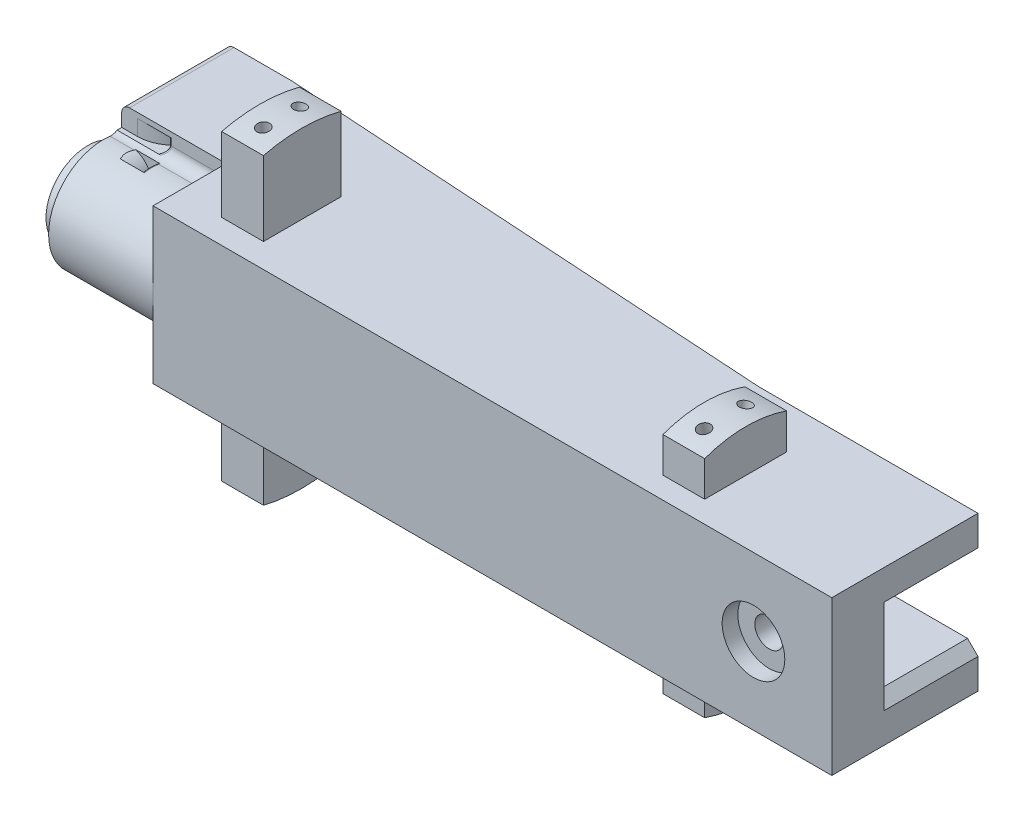
SolidWorks part; units mm, degrees
material "ABS"
ref_plane "Plan de face" through (0, 0, 0) normal (0, 0, 1) x (1, 0, 0)
ref_plane "Plan de dessus" through (0, 0, 0) normal (0, 1, 0) x (1, 0, 0)
ref_plane "Plan de droite" through (0, 0, 0) normal (1, 0, 0) x (0, 0, -1)
sketch "Esquisse1" plane through (0, 0, 0) normal (0, 0, 1) x (1, 0, 0)
  line L0 (-150, -14.75) -> (-150, 14.75)
  line L1 (-150, 14.75) -> (0, 14.75)
  line L2 (0, 14.75) -> (0, -14.75)
  line L3 (-150, 0) -> (0, 0) construction
  line L4 (-150, -14.75) -> (0, -14.75)
  dimension "D1" = 29.5
  dimension "D2" = 150
extrude "ForearmMain" add sketch "Esquisse1" along normal blind 34
ref_plane "Plan1" through (0, 0, 0) normal (0, -1, 0) x (-1, 0, 0)
ref_plane "Plan2" through (0, 0, 23.5) normal (0, 0, -1) x (-1, 0, 0)
sketch "Esquisse2" plane through (-150, 0, 0) normal (-1, 0, 0) x (0, 0, 1)
  line L0 (0, 14.75) -> (0, -14.75) construction
  line L1 (20, 9.8995) -> (20, 14.75)
  line L2 (0, 0) -> (49.5, 0) construction
  line L3 (20, 14.75) -> (49.5, 14.75)
  line L4 (49.5, 14.75) -> (49.5, -14.75)
  line L5 (49.5, -14.75) -> (20, -14.75)
  line L6 (20, -14.75) -> (20, -9.8995)
  line L7 (34, 14.75) -> (0, 14.75) construction
  line L8 (34, -14.75) -> (0, -14.75) construction
  arc A0 (20, -9.8995) -> (20, 9.8995) centre (23.5, 0) ccw
  point P8 (20, 12.3247)
  point P13 (20, -12.3247)
  dimension "D1" = 10.5
  dimension "D2" = 23.5
  dimension "D3" = 3.5
extrude "Enlèv. mat.-Extru.1" cut sketch "Esquisse2" against normal blind 20
sketch "Esquisse3" plane through (-150, 0, 0) normal (-1, 0, 0) x (0, 0, 1)
  circle A0 centre (23.5, 0) radius 8
  dimension "D1" = 16
extrude "Boss.-Extru.2" add sketch "Esquisse3" along normal blind 3
sketch "Esquisse4" plane through (-153, 0, 0) normal (-1, 0, 0) x (0, 0, 1)
  line L1 (0, 0) -> (45.6879, 0) construction
  circle A0 centre (29, 0) radius 1.025
  circle A1 centre (23.5, 0) radius 8 construction
  dimension "D1" = 2.05
  dimension "D2" = 5.5
extrude "Enlèv. mat.-Extru.2" cut sketch "Esquisse4" against normal blind 10
chamfer "Chanfrein1" distance 0.3 angle 45 1 edges at (-153, 0, 30.025)
pattern_circular "Répétition circulaire1" count 3 over 360 about axis through (-153, 0, 23.5) along (-1, 0, 0) of "Chanfrein1", "Enlèv. mat.-Extru.2"
fillet "Congé1" radius 2 2 edges at (-140, 9.8995, 20) (-140, -9.8995, 20)
sketch "Esquisse5" plane through (0, -14.75, 0) normal (0, -1, 0) x (-1, 0, 0)
  line L0 (147, 0) -> (150, 0)
  line L1 (150, -20) -> (147, -20)
  line L2 (150, -31.5) -> (150, -15.5) construction
  line L3 (140, -13) -> (140, -7)
  line L4 (150, -20) -> (150, -22.5)
  line L5 (150, -22.5) -> (148.5, -22.5)
  line L6 (137.5, -11.5) -> (137.5, -8.5)
  line L7 (130, -20) -> (150, -20) construction
  line L8 (150, -20) -> (150, 0) construction
  line L9 (150, 0) -> (150, 2.5)
  line L10 (150, 2.5) -> (148.5, 2.5)
  line L11 (150, 0) -> (0, 0) construction
  arc A0 (140, -13) -> (147, -20) centre (147, -13) ccw
  arc A1 (137.5, -11.5) -> (148.5, -22.5) centre (148.5, -11.5) ccw
  arc A2 (140, -7) -> (147, 0) centre (147, -7) cw
  arc A3 (137.5, -8.5) -> (148.5, 2.5) centre (148.5, -8.5) cw
  dimension "D4" = 7
  dimension "D5" = 11
  dimension "D6" = 7
  dimension "D7" = 11
  dimension "D1" = 2.5
  dimension "D2" = 2.5
  dimension "D3" = 10
  dimension "D8" = 2.5
extrude "ZiptieHole1" cut sketch "Esquisse5" against normal blind 3 from offset 1 offset against normal yes
mirror "ZiptieSymmetry" about plane through (0, 0, 0) normal (0, -1, 0) of "ZiptieHole1"
sketch "Esquisse6" plane through (0, 0, 34) normal (0, 0, 1) x (1, 0, 0)
  line L0 (-57.8936, 10.7) -> (-119.0286, 10.7) construction
  line L1 (-57.0745, 0) -> (-113.5036, 0) construction
  line L2 (-139.5, -5.2) -> (-139.5, 5.2)
  line L3 (-147.5, 13.2) -> (-162, 13.2)
  line L4 (-162, 13.2) -> (-162, 10.7)
  line L5 (-13.475, 0) -> (13.475, 0) construction
  line L6 (-162, -10.7) -> (-147, -10.7)
  line L7 (-162, 10.7) -> (-147, 10.7)
  line L8 (-142, 5.7) -> (-142, -5.7)
  line L9 (-162, -13.2) -> (-162, -10.7)
  line L10 (-147.5, -13.2) -> (-162, -13.2)
  line L11 (-150, 10.5) -> (-150, -10.5) construction
  arc A0 (-147, 10.7) -> (-142, 5.7) centre (-147, 5.7) cw
  arc A1 (-139.5, 5.2) -> (-147.5, 13.2) centre (-147.5, 5.2) ccw
  arc A2 (-139.5, -5.2) -> (-147.5, -13.2) centre (-147.5, -5.2) cw
  arc A3 (-147, -10.7) -> (-142, -5.7) centre (-147, -5.7) ccw
  point P23 (-142, 0)
  point P25 (-139.5, 0)
  dimension "D1" = 5
  dimension "D4" = 8
  dimension "D2" = 10.7
  dimension "D3" = 2.5
  dimension "D5" = 2.5
  dimension "D6" = 8
  dimension "D7" = 20
extrude "ZiptieHole2" cut sketch "Esquisse6" against normal blind 3 from offset 9 offset against normal yes
fillet "Congé3" radius 1.5 2 edges at (-150, 14.75, 10) (-150, -14.75, 10)
fillet "Congé13" radius 0.4 9 edges at (-141.5179, -13.0798, 20) (-141.7114, -11.6368, 20.1554) (-141.5179, -12.25, 0) (-141.5179, 12.25, 0) (-141.7114, 11.6368, 20.1554)
ref_plane "BackScrewsPlane" through (-117.5, 0, 0) normal (-1, 0, 0) x (0, 0, 1)
ref_plane "FrontScrewsPlane" through (-32.5, 0, 0) normal (-1, 0, 0) x (0, 0, 1)
sketch "Esquisse7" plane through (-32.5, 0, 0) normal (-1, 0, 0) x (0, 0, 1)
  line L0 (16.9395, 22.3646) -> (21.9137, 23.2417) construction
  line L1 (21.9137, 23.2417) -> (27.0552, 22.3351) construction
  line L2 (25.972, 22.5261) -> (25.972, -22.5261) construction
  line L3 (27.0552, -22.335) -> (21.9136, -23.2417) construction
  line L4 (21.9136, -23.2417) -> (16.9395, -22.3646) construction
  line L5 (18.0228, -22.5556) -> (18.0228, 22.5556) construction
  line L6 (16.9395, 22.3646) -> (21.9137, 23.2417) construction
  line L7 (21.9137, 23.2417) -> (27.0552, 22.3351) construction
  line L8 (25.972, 22.5261) -> (25.972, -22.5261) construction
  line L9 (27.0552, -22.335) -> (21.9136, -23.2417) construction
  line L10 (21.9136, -23.2417) -> (16.9395, -22.3646) construction
  line L11 (18.0228, -22.5556) -> (18.0228, 22.5556) construction
  line L12 (18.0228, -22.5556) -> (19.2697, -15.4845) construction
  line L13 (25.972, -22.5261) -> (24.7953, -15.8529) construction
  line L14 (14.1382, -21.5513) -> (14.1382, -14.75)
  line L15 (14.1382, -14.75) -> (29.8513, -14.75)
  line L16 (29.8513, -14.75) -> (29.8513, -21.492)
  line L17 (14.1382, -14.75) -> (0, -14.75) construction
  arc A0 (14.1382, -21.5513) -> (29.8513, -21.492) centre (21.9117, 0.5007) ccw
  dimension "D1" = 4
  dimension "D2" = 4
extrude "Boss.-Extru.3" add sketch "Esquisse7" against normal mid plane 8 contours L14 A0 L16 L15
ref_plane "Plan7" through (-32.5, -22.5556, 18.0228) normal (0, 0.9848, 0.1736) x (1, 0, 0)
ref_plane "Plan8" through (-32.5, -22.5261, 25.972) normal (0, 0.9848, -0.1736) x (1, 0, 0)
hole_wizard "Dégagement M23" positions "Esquisse30" profile "Esquisse31" hole size "M2" standard "Ansi Metric"
sketch "Esquisse30" plane through (-32.5, -22.5556, 18.0228) normal (0, 0.9848, 0.1736) x (1, 0, 0)
  point P0 (0, 0)
sketch "Esquisse31" plane through (-32.5, -22.5556, 18.0228) normal (1, 0, 0) x (0, 0.1736, -0.9848)
  line L0 (0, 0) -> (0, 12)
  line L1 (0, 12) -> (1.2, 12)
  line L2 (1.2, 12) -> (1.2, 0)
  line L4 (1.2, 0) -> (0, 0) construction
  line L5 (1.2, 0) -> (0, 0) construction
  line L6 (1.2, 0) -> (1.2, -1.2)
  line L7 (1.2, -1.2) -> (0, -1.2)
  line L8 (0, 0) -> (0, -1.2)
  line L10 (0, 12) -> (-1.2, 12) construction
  line L11 (0, -6.35) -> (0, 107.95) construction
  dimension "Diamètre du perçage" = 2.4
  dimension "Profondeur du perçage" = 12
  dimension "Angle de pointe" = 180
hole_wizard "Dégagement M24" positions "Esquisse32" profile "Esquisse33" hole size "M2" standard "Ansi Metric"
sketch "Esquisse32" plane through (-32.5, -22.5261, 25.972) normal (0, 0.9848, -0.1736) x (1, 0, 0)
  point P0 (0, 0)
sketch "Esquisse33" plane through (-32.5, -22.5261, 25.972) normal (1, 0, 0) x (0, -0.1736, -0.9848)
  line L0 (0, 0) -> (0, 12)
  line L1 (0, 12) -> (1.2, 12)
  line L2 (1.2, 12) -> (1.2, 0)
  line L5 (1.2, 0) -> (0, 0)
  line L10 (0, 12) -> (-1.2, 12) construction
  line L11 (0, -6.35) -> (0, 107.95) construction
  dimension "Diamètre du perçage" = 2.4
  dimension "Profondeur du perçage" = 12
  dimension "Angle de pointe" = 180
sketch "Esquisse34" plane through (-32.5, -22.5556, 18.0228) normal (0, 0.9848, 0.1736) x (1, 0, 0)
  line L0 (-1.1836, 2.05) -> (-4, 2.05)
  line L1 (-1.1836, 2.05) -> (-2.3671, 0) construction
  line L2 (-2.3671, 0) -> (-1.1836, -2.05) construction
  line L3 (-1.1836, -2.05) -> (1.1836, -2.05)
  line L4 (1.1836, -2.05) -> (2.3671, 0)
  line L5 (2.3671, 0) -> (1.1836, 2.05)
  line L6 (1.1836, 2.05) -> (-1.1836, 2.05)
  line L7 (-4, 2.05) -> (-4, -2.05)
  line L8 (-4, -2.05) -> (-1.1836, -2.05)
  line L9 (-4, 5.181) -> (-4, -10.2934) construction
  circle A0 centre (0, 0) radius 2.05 construction
  dimension "D1" = 4.1
extrude "Enlèv. mat.-Extru.9" cut sketch "Esquisse34" along normal blind 1.7 from offset 3
sketch "Esquisse35" plane through (-32.5, -22.5261, 25.972) normal (0, 0.9848, -0.1736) x (1, 0, 0)
  line L0 (-1.1836, 2.05) -> (-4, 2.05)
  line L1 (-1.1836, 2.05) -> (-2.3671, 0) construction
  line L2 (-2.3671, 0) -> (-1.1836, -2.05) construction
  line L3 (-1.1836, -2.05) -> (1.1836, -2.05)
  line L4 (1.1836, -2.05) -> (2.3671, 0)
  line L5 (2.3671, 0) -> (1.1836, 2.05)
  line L6 (1.1836, 2.05) -> (-1.1836, 2.05)
  line L7 (-4, 2.05) -> (-4, -2.05)
  line L8 (-4, -2.05) -> (-1.1836, -2.05)
  line L9 (-4, 10.3037) -> (-4, -5.1707) construction
  circle A0 centre (0, 0) radius 2.05 construction
  dimension "D1" = 4.1
extrude "Enlèv. mat.-Extru.10" cut sketch "Esquisse35" along normal blind 1.7 from offset 3
sketch "Esquisse8" plane through (-117.5, 0, 0) normal (-1, 0, 0) x (0, 0, 1)
  line L0 (18.4, 29.658) -> (18.4, -29.658) construction
  line L1 (17.3082, 29.5239) -> (21.5245, 30.0416) construction
  line L2 (21.5245, 30.0416) -> (26.4958, 29.6067) construction
  line L3 (25.4, -29.7025) -> (25.4, 29.7025) construction
  line L4 (17.3082, -29.5239) -> (21.5244, -30.0416) construction
  line L5 (21.5244, -30.0416) -> (26.4958, -29.6067) construction
  line L6 (18.4, 29.658) -> (18.4, -29.658) construction
  line L7 (17.3082, 29.5239) -> (21.5245, 30.0416) construction
  line L8 (21.5245, 30.0416) -> (26.4958, 29.6067) construction
  line L9 (25.4, -29.7025) -> (25.4, 29.7025) construction
  line L10 (17.3082, -29.5239) -> (21.5244, -30.0416) construction
  line L11 (21.5244, -30.0416) -> (26.4958, -29.6067) construction
  line L12 (18.4, -29.658) -> (19.1128, -23.8524) construction
  line L13 (25.4, -29.7025) -> (24.8905, -23.8789) construction
  line L14 (14.4621, -28.9072) -> (14.4621, -14.75)
  line L15 (14.4621, -14.75) -> (29.3538, -14.75)
  line L16 (29.3538, -14.75) -> (29.3538, -29.0003)
  line L17 (14.4621, -14.75) -> (0, -14.75) construction
  arc A0 (14.4621, -28.9072) -> (29.3538, -29.0003) centre (22.0915, 0.4069) ccw
  dimension "a" = 4
  dimension "D2" = 4
extrude "Boss.-Extru.4" add sketch "Esquisse8" against normal mid plane 8
ref_plane "Plan4" through (-117.5, -29.658, 18.4) normal (0, 0.9925, 0.1219) x (1, 0, 0)
ref_plane "Plan5" through (-117.5, -29.7025, 25.4) normal (0, 0.9962, -0.0872) x (1, 0, 0)
hole_wizard "Dégagement M21" positions "Esquisse24" profile "Esquisse25" hole size "M2" standard "Ansi Metric"
sketch "Esquisse24" plane through (-117.5, -29.658, 18.4) normal (0, 0.9925, 0.1219) x (1, 0, 0)
  point P0 (0, 0)
sketch "Esquisse25" plane through (-117.5, -29.658, 18.4) normal (1, 0, 0) x (0, 0.1219, -0.9925)
  line L0 (0, 0) -> (0, 12)
  line L1 (0, 12) -> (1.2, 12)
  line L2 (1.2, 12) -> (1.2, 0)
  line L5 (1.2, 0) -> (0, 0)
  line L10 (0, 12) -> (-1.2, 12) construction
  line L11 (0, -6.35) -> (0, 107.95) construction
  dimension "Diamètre du perçage" = 2.4
  dimension "Profondeur du perçage" = 12
  dimension "Angle de pointe" = 180
hole_wizard "Dégagement M22" positions "Esquisse26" profile "Esquisse27" hole size "M2" standard "Ansi Metric"
sketch "Esquisse26" plane through (-117.5, -29.7025, 25.4) normal (0, 0.9962, -0.0872) x (1, 0, 0)
  point P0 (0, 0)
sketch "Esquisse27" plane through (-117.5, -29.7025, 25.4) normal (1, 0, 0) x (0, -0.0872, -0.9962)
  line L0 (0, 0) -> (0, 12)
  line L1 (0, 12) -> (1.2, 12)
  line L2 (1.2, 12) -> (1.2, 0)
  line L4 (1.2, 0) -> (0, 0) construction
  line L5 (1.2, 0) -> (0, 0) construction
  line L6 (1.2, 0) -> (1.2, -1.2)
  line L7 (1.2, -1.2) -> (0, -1.2)
  line L8 (0, 0) -> (0, -1.2)
  line L10 (0, 12) -> (-1.2, 12) construction
  line L11 (0, -6.35) -> (0, 107.95) construction
  dimension "Diamètre du perçage" = 2.4
  dimension "Profondeur du perçage" = 12
  dimension "Angle de pointe" = 180
sketch "Esquisse28" plane through (-117.5, -29.658, 18.4) normal (0, 0.9925, 0.1219) x (1, 0, 0)
  line L0 (-1.1836, 2.05) -> (-4, 2.05)
  line L1 (-1.1836, 2.05) -> (-2.3671, 0) construction
  line L2 (-2.3671, 0) -> (-1.1836, -2.05) construction
  line L3 (-1.1836, -2.05) -> (1.1836, -2.05)
  line L4 (1.1836, -2.05) -> (2.3671, 0)
  line L5 (2.3671, 0) -> (1.1836, 2.05)
  line L6 (1.1836, 2.05) -> (-1.1836, 2.05)
  line L7 (-4, 2.05) -> (-4, -2.05)
  line L8 (-4, -2.05) -> (-1.1836, -2.05)
  line L9 (-4, -9.0554) -> (-4, 5.7253) construction
  circle A0 centre (0, 0) radius 2.05 construction
  dimension "D1" = 4.1
extrude "Enlèv. mat.-Extru.7" cut sketch "Esquisse28" along normal blind 1.7 from offset 3
sketch "Esquisse29" plane through (-117.5, -29.7025, 25.4) normal (0, 0.9962, -0.0872) x (1, 0, 0)
  line L0 (-1.1836, 2.05) -> (-4, 2.05)
  line L1 (-1.1836, 2.05) -> (-2.3671, 0) construction
  line L2 (-2.3671, 0) -> (-1.1836, -2.05) construction
  line L3 (-1.1836, -2.05) -> (1.1836, -2.05)
  line L4 (1.1836, -2.05) -> (2.3671, 0)
  line L5 (2.3671, 0) -> (1.1836, 2.05)
  line L6 (1.1836, 2.05) -> (-1.1836, 2.05)
  line L7 (-4, 2.05) -> (-4, -2.05)
  line L8 (-4, -2.05) -> (-1.1836, -2.05)
  line L9 (-4, -5.242) -> (-4, 9.593) construction
  circle A0 centre (0, 0) radius 2.05 construction
  dimension "D1" = 4.1
extrude "Enlèv. mat.-Extru.8" cut sketch "Esquisse29" along normal blind 1.7 from offset 3
mirror "ScrewsMountSymmetry" about plane through (0, 0, 0) normal (0, 1, 0) of "Enlèv. mat.-Extru.8", "Enlèv. mat.-Extru.7", "Dégagement M22", "Dégagement M21", "Boss.-Extru.4", "Enlèv. mat.-Extru.10", "Enlèv. mat.-Extru.9", "Dégagement M24", "Dégagement M23", "Boss.-Extru.3"
sketch "Esquisse10" plane through (0, 0, 0) normal (0, -1, 0) x (-1, 0, 0)
  line L0 (137.3923, 0) -> (127, -6)
  line L1 (127, -6) -> (0, -6)
  line L2 (0, -6) -> (0, 0)
  line L3 (0, 0) -> (137.3923, 0)
  line L5 (150, 0) -> (0, 0) construction
  dimension "D1" = 30
  dimension "D2" = 23
  dimension "D3" = 6
extrude "Enlèv. mat.-Extru.6" cut sketch "Esquisse10" against normal through all both and the other way through all contours L0 L1 L2 L3
sketch "Esquisse20" plane through (0, 14.75, 0) normal (0, 1, 0) x (1, 0, 0)
  line L0 (-137.3923, 0) -> (-127, -6)
  line L1 (-127, -6) -> (-42, -6)
  line L3 (-42, -6) -> (-137.3923, 0)
  line L4 (0, -34) -> (0, -6) construction
  line L5 (-127, -6) -> (0, -6) construction
  dimension "D1" = 42
extrude "Boss.-Extru.5" add sketch "Esquisse20" against normal blind 6
mirror "Symétrie2" about plane through (0, 0, 0) normal (0, 1, 0) of "Boss.-Extru.5"
sketch "Esquisse21" plane through (0, 0, 6) normal (0, 0, -1) x (-1, 0, 0)
  line L0 (-13.475, 0) -> (13.475, 0) construction
  text T0 "<b>LARSEN Team</b>" font "Century Gothic" height 10
  dimension "D1" = 4.7
extrude "LARSENTeamCut" cut sketch "Esquisse21" against normal blind 0.5
sketch "Esquisse11" plane through (0, 0, 0) normal (1, 0, 0) x (0, 0, -1)
  line L0 (-6, 14.75) -> (-6, -14.75) construction
  line L1 (-6, 7) -> (-22, 7)
  line L2 (-6, 7) -> (-6, -7)
  line L3 (-6, -7) -> (-22, -7)
  line L4 (-22, 7) -> (-22, -7)
  dimension "D1" = 14
  dimension "D2" = 7
  dimension "D3" = 16
extrude "ExtensionPort" cut sketch "Esquisse11" against normal blind 25
chamfer "Chanfrein6" distance 2 angle 45 3 edges at (0, 7, 14) (0, 0, 22) (0, -7, 14)
hole_wizard "Chambrage pour vis à tête hexagonale M51" positions "Esquisse14" profile "Esquisse13" counterbore size "M5" standard "ISO" end condition through all
sketch "Esquisse14" plane through (0, 0, 34) normal (0, 0, 1) x (1, 0, 0)
  line L0 (0, 0) -> (-13.7267, 0) construction
  line L2 (0, 7) -> (0, -7) construction
  point P0 (-15, 0)
  dimension "D1" = 15
sketch "Esquisse13" plane through (-15, 0, 34) normal (1, 0, 0) x (0, -1, 0)
  line L0 (0, 0) -> (0, 34)
  line L1 (0, 34) -> (2.75, 34)
  line L3 (2.75, 34) -> (2.75, 3)
  line L4 (2.75, 3) -> (6, 3)
  line L5 (6, 3) -> (6, 0)
  line L7 (6, 0) -> (0, 0)
  line L11 (0, -6.35) -> (0, 107.95) construction
  dimension "Diamètre du perçage jusqu'au prochain" = 5.5
  dimension "Profondeur du perçage jusqu'au prochain" = 34
  dimension "Diamètre du chambrage" = 12
  dimension "Profondeur du chambrage" = 3
sketch "Esquisse37" plane through (0, -14.75, 0) normal (0, -1, 0) x (1, 0, 0)
  line L0 (-130, 34) -> (0, 34) construction
  line L1 (-36.5, 14.1382) -> (-36.5, 29.8513) construction
  line L2 (-28.5, 6) -> (-28.5, 34)
  line L3 (-28.5, 14.1382) -> (-28.5, 29.8513) construction
  line L4 (-36.5, 6) -> (-36.5, 34)
  line L5 (0, 6) -> (-42, 6) construction
  line L6 (-36.5, 34) -> (-28.5, 34)
  line L7 (-28.5, 6) -> (-36.5, 6)
extrude "RapidProtoUglyCutFront" [suppressed] cut sketch "Esquisse37" along normal through all both and the other way through all flip side to cut
sketch "Esquisse36" plane through (0, -14.75, 0) normal (0, -1, 0) x (1, 0, 0)
  line L3 (-113.5, 29.3538) -> (-113.5, 14.4621) construction
  line L5 (-121.5, 29.3538) -> (-121.5, 14.4621) construction
  line L6 (-130, 34) -> (0, 34) construction
  line L7 (-113.5, 34) -> (-113.5, 1.5028)
  line L8 (-42, 6) -> (-137.3923, 0) construction
  line L9 (-121.5, 34) -> (-121.5, 0.9996)
  line L10 (-121.5, 34) -> (-113.5, 34)
  line L11 (-113.5, 1.5028) -> (-121.5, 0.9996)
extrude "RapidProtUglyCutBack" [suppressed] cut sketch "Esquisse36" against normal through all both and the other way through all flip side to cut
equation "\"ScrewSpace\"= 3.5mm"
